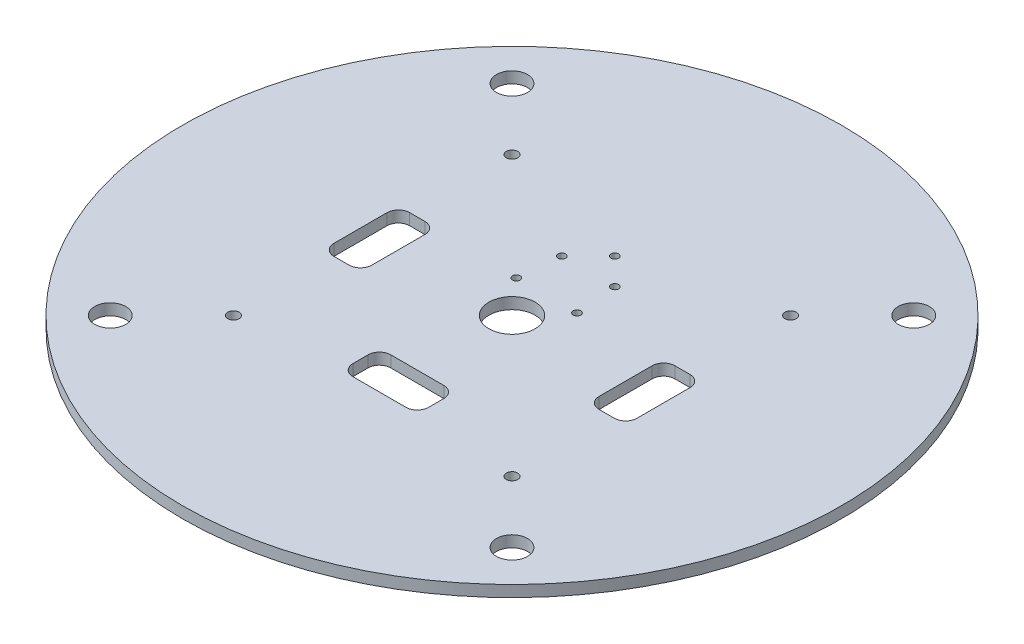
SolidWorks part; units mm, degrees
ref_plane "前视基准面" through (0, 0, 0) normal (0, 0, 1) x (1, 0, 0)
ref_plane "上视基准面" through (0, 0, 0) normal (0, 1, 0) x (1, 0, 0)
ref_plane "右视基准面" through (0, 0, 0) normal (1, 0, 0) x (0, 0, -1)
sketch "草图1" plane through (0, 0, 0) normal (0, 1, 0) x (1, 0, 0)
  circle A0 centre (0, 0) radius 87
  dimension "D1" = 174
base flange "基体-法兰1" sketch "草图1" thickness 3 reverse thickness direction no parameters "D1"=0.7366
sketch "草图6" plane through (0, 0, 0) normal (0, 1, 0) x (1, 0, 0)
  line L0 (0, 87) -> (0, -87) construction
  line L1 (10, -10.35) -> (-10, -10.35) construction
  line L2 (10, -10.35) -> (10, 29.65) construction
  line L3 (10, 29.65) -> (-10, 29.65) construction
  line L4 (-10, -10.35) -> (-10, 29.65) construction
  line L5 (10, -10.35) -> (-10, 29.65) construction
  line L6 (10, 29.65) -> (-10, -10.35) construction
  line L7 (-87, 0) -> (87, 0) construction
  line L8 (-10, 9.65) -> (10, 9.65) construction
  line L9 (-53.033, 53.033) -> (53.033, -53.033) construction
  line L10 (-30, 10) -> (-40, 10)
  line L11 (30, -10) -> (40, -10)
  line L12 (30, -10) -> (30, 10)
  line L13 (30, 10) -> (40, 10)
  line L14 (40, -10) -> (40, 10)
  line L15 (30, -10) -> (40, 10) construction
  line L16 (30, 10) -> (40, -10) construction
  line L17 (-40, -10) -> (-40, 10)
  line L18 (-30, -10) -> (-40, -10)
  line L19 (-30, -10) -> (-30, 10)
  line L20 (-53.033, -53.033) -> (0, 0) construction
  line L21 (10, -35) -> (-10, -35)
  line L22 (10, -35) -> (10, -25)
  line L23 (10, -25) -> (-10, -25)
  line L24 (-10, -35) -> (-10, -25)
  line L25 (10, -35) -> (-10, -25) construction
  line L26 (10, -25) -> (-10, -35) construction
  circle A0 centre (0, 0) radius 6.1
  circle A1 centre (0, 0) radius 87 construction
  circle A12 centre (-8, 9.15) radius 1
  circle A13 centre (-7, 20.15) radius 1
  circle A14 centre (53.033, 53.033) radius 4.1
  circle A15 centre (-53.033, 53.033) radius 4.1
  circle A16 centre (53.033, -53.033) radius 4.1
  circle A17 centre (-53.033, -53.033) radius 4.1
  circle A18 centre (8, 9.15) radius 1
  circle A19 centre (7, 20.15) radius 1
  circle A20 centre (0, 27.15) radius 1
  circle A21 centre (-36.7696, -36.7696) radius 1.5
  circle A22 centre (-36.7696, 36.7696) radius 1.5
  circle A23 centre (36.7696, 36.7696) radius 1.5
  circle A24 centre (36.7696, -36.7696) radius 1.5
  point P3 (0, 9.65)
  point P26 (0, -30)
  point P32 (35, 0)
  point P39 (0, 0)
  point P60 (0, 0)
  dimension "D1" = 12.2
  dimension "D4" = 2
  dimension "D9" = 8.2
  dimension "D10" = 8.2
  dimension "D12" = 8.2
  dimension "D5" = 2
  dimension "D18" = 2
  dimension "D23" = 3
  dimension "D2" = 40
  dimension "D3" = 20
  dimension "D6" = 8
  dimension "D8" = 10.35
  dimension "D11" = 75
  dimension "D13" = 10
  dimension "D14" = 20
  dimension "D15" = 35
  dimension "D16" = 20.5
  dimension "D7" = 7
  dimension "D17" = 9.5
  dimension "D19" = 2.5
  dimension "D20" = 10
  dimension "D21" = 20
  dimension "D22" = 30
  dimension "D24" = 52
  dimension "D25" = 4
extrude "切除-拉伸1" cut sketch "草图6" against normal up to next normal cut yes
fillet "圆角1" radius 3 12 edges at (40, -1.5, 10) (30, -1.5, 10) (40, -1.5, -10) (30, -1.5, -10) (-30, -1.5, 10) (-40, -1.5, 10) (-30, -1.5, -10) (-40, -1.5, -10) (10, -1.5, 35) (10, -1.5, 25) (-10, -1.5, 25) (-10, -1.5, 35)
sketch "折弯-线1" plane through (0, 0, 0) normal (0, 1, 0) x (1, 0, 0)
sketch "边界框1" plane through (0, 0, 0) normal (0, 1, 0) x (1, 0, 0)
sheet metal parameters "钣金6" thickness 3 parameters "D1"=0.7366
flat pattern "平板型式6" [suppressed]
sketch "折弯-线2" plane through (0, 0, 0) normal (0, 1, 0) x (1, 0, 0)
sketch "边界框2" [suppressed] plane through (0, 0, 0) normal (0, 1, 0) x (1, 0, 0)
sheet metal parameters "钣金7" thickness 3 parameters "D1"=0.7366
flat pattern "平板型式6"
sketch "折弯-线2" plane through (0, 0, 0) normal (0, 1, 0) x (1, 0, 0)
sketch "边界框2" [suppressed] plane through (0, 0, 0) normal (0, 1, 0) x (1, 0, 0)
